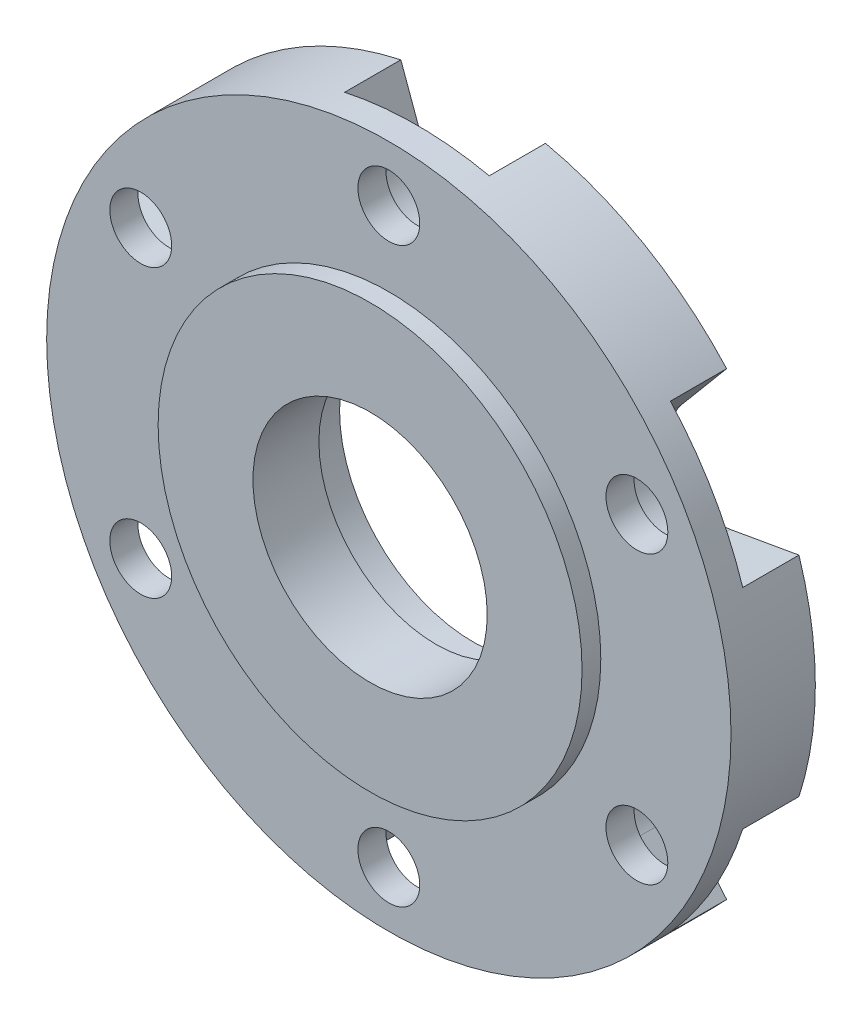
SolidWorks part; units mm, degrees
material "6061-T6 (SS)"
ref_plane "Front Plane" through (0, 0, 0) normal (0, 0, 1) x (1, 0, 0)
ref_plane "Top Plane" through (0, 0, 0) normal (0, 1, 0) x (1, 0, 0)
ref_plane "Right Plane" through (0, 0, 0) normal (1, 0, 0) x (0, 0, -1)
sketch "Sketch Spindle Skeleton" plane through (0, 0, 0) normal (1, 0, 0) x (0, 0, -1)
  line L0 (-95.847, -9.525) -> (-140.95, -9.525)
  line L5 (-1000, 0) -> (49000, 0)
  line L6 (0, -9.525) -> (0, 9.525)
  line L13 (0, 9.525) -> (-45.847, 9.525)
  line L26 (-45.847, 9.525) -> (-45.847, 14)
  line L27 (-45.847, 14) -> (-95.847, 14)
  line L32 (-95.847, 14) -> (-95.847, 9.525)
  line L34 (-160, 7) -> (-160, -7)
  line L36 (-95.847, -9.525) -> (-95.847, -14)
  line L37 (-95.847, -14) -> (-45.847, -14)
  line L38 (-45.847, -14) -> (-45.847, -9.525)
  line L39 (0, -9.525) -> (-45.847, -9.525)
  line L40 (-25.305, 36.5125) -> (-16.305, 36.5125)
  line L41 (-111.341, 22.6187) -> (-95.847, 22.6187)
  line L42 (-111.341, 22.6187) -> (-111.341, -22.6187)
  line L43 (-111.341, -22.6187) -> (-95.847, -22.6187)
  line L44 (-95.847, 22.6187) -> (-95.847, -22.6187)
  line L45 (-111.341, 22.6187) -> (-95.847, -22.6187) construction
  line L46 (-111.341, -22.6187) -> (-95.847, 22.6187) construction
  line L47 (-30.353, 22.6187) -> (-45.847, 22.6187)
  line L48 (-30.353, 22.6187) -> (-30.353, -22.6187)
  line L49 (-30.353, -22.6187) -> (-45.847, -22.6187)
  line L50 (-45.847, 22.6187) -> (-45.847, -22.6187)
  line L51 (-30.353, 22.6187) -> (-45.847, -22.6187) construction
  line L52 (-30.353, -22.6187) -> (-45.847, 22.6187) construction
  line L59 (-16.305, 36.5125) -> (-16.305, -36.5125)
  line L60 (-16.305, -36.5125) -> (-25.305, -36.5125)
  line L61 (-25.305, -22.6187) -> (-27.305, -22.6187)
  line L62 (-27.305, -22.6187) -> (-27.305, -12.5)
  line L63 (-27.305, -12.5) -> (-25.305, -12.5)
  line L64 (-25.305, -12.5) -> (-25.305, 12.5)
  line L65 (-25.305, 12.5) -> (-27.305, 12.5)
  line L66 (-27.305, 12.5) -> (-27.305, 22.6187)
  line L67 (-27.305, 22.6187) -> (-25.305, 22.6187)
  line L68 (-25.305, 22.6187) -> (-25.305, 36.5125)
  line L69 (-25.305, -22.6187) -> (-25.305, -36.5125)
  line L71 (-119.469, 36.5125) -> (-26.305, 36.5125)
  line L72 (-119.469, 36.5125) -> (-119.469, -36.5125)
  line L73 (-119.469, -36.5125) -> (-26.305, -36.5125)
  line L74 (-26.305, 36.5125) -> (-26.305, -36.5125)
  line L75 (-119.469, 36.5125) -> (-26.305, -36.5125) construction
  line L76 (-119.469, -36.5125) -> (-26.305, 36.5125) construction
  line L77 (-140.95, -9.525) -> (-140.95, -7)
  line L78 (-140.95, -7) -> (-160, -7)
  line L79 (-95.847, 9.525) -> (-140.95, 9.525)
  line L80 (-140.95, 7) -> (-160, 7)
  line L81 (-140.95, 9.525) -> (-140.95, 7)
  line L82 (-118.3985, 9.525) -> (-118.3985, -9.525) construction
  line L83 (-22.9235, 9.525) -> (-22.9235, -9.525) construction
  line L96 (-119.469, 36.5125) -> (-134.709, 36.5125)
  line L98 (-119.469, -36.5125) -> (-134.709, -36.5125)
  line L99 (-134.709, 36.5125) -> (-134.709, -36.5125)
  line L110 (-119.469, 36.5125) -> (-119.469, -36.5125)
  point P3 (0, 0)
  point P18 (-103.594, 0)
  point P24 (-38.1, 0)
  point P29 (-72.887, 0)
  point P48 (-16.305, 30.5656)
  point P70 (-134.709, 31.75)
revolve "Main Revolve" add sketch "Sketch Spindle Skeleton" angle 360 about L5 region at (0, 22.8004, 21.005) region at (0, 17.5594, 26.805)
sketch "Sketch Center Cut" plane through (0, 0, 25.305) normal (0, 0, 1) x (1, 0, 0)
  circle A3 centre (0, 0) radius 12.5
  dimension "D1" = 25
extrude "Cut Center" cut sketch "Sketch Center Cut" against normal through all both and the other way through all
hole_wizard "CBORE for M6 SHCS1" positions "Hole wizard sketch 1" profile "Hole wizard sketch 2" counterbore size "M6" standard "ANSI Metric" end condition through all
sketch "Hole wizard sketch 1" plane through (0, 0, 16.305) normal (0, 0, -1) x (-1, 0, 0)
  point P0 (0, 30.5656)
sketch "Hole wizard sketch 2" plane through (0, 30.5656, 16.305) normal (1, 0, 0) x (0, 1, 0)
  line L0 (0, 0) -> (0, 11)
  line L1 (0, 11) -> (3.3, 11)
  line L3 (3.3, 11) -> (3.3, 6)
  line L4 (3.3, 6) -> (5.5, 6)
  line L5 (5.5, 6) -> (5.5, 0)
  line L7 (5.5, 0) -> (0, 0)
  line L11 (0, -6.35) -> (0, 107.95) construction
  dimension "Thru Hole Dia." = 6.6
  dimension "Thru Hole Depth" = 11
  dimension "C'Bore Dia." = 11
  dimension "C'Bore Depth" = 6
pattern_circular "CirPattern1" count 6 over 360 about axis through (0, 0, 16.305) along (0, 0, 1) of "CBORE for M6 SHCS1"
sketch "Sketch1" plane through (0, 0, 16.305) normal (0, 0, -1) x (-1, 0, 0)
  circle A0 centre (0, 0) radius 14.2558
  dimension "D1" = 28.5115
extrude "Cut-Extrude1" cut sketch "Sketch1" against normal blind 3.9624
sketch "Sketch2" plane through (0, 0, 16.305) normal (0, 0, -1) x (-1, 0, 0)
  line L0 (-5.1683, 28.6845) -> (-7.7172, 35.6876)
  line L1 (0, 30.5656) -> (0, 37.65) construction
  line L2 (5.1683, 28.6845) -> (7.7172, 35.6876)
  circle A0 centre (0, 30.5656) radius 5.5 construction
  circle A1 centre (0, 0) radius 36.5125 construction
  arc A2 (-5.1683, 28.6845) -> (5.1683, 28.6845) centre (0, 30.5656) ccw
  point P37 (0.065, 0.0375)
  circle M8 centre (0, 30.5656) radius 5.5
  circle M9 centre (0, 0) radius 36.5125
  dimension "D1" = 20
extrude "Cut-Extrude2" cut sketch "Sketch2" against normal up to surface (6 mm away) contours L1 L2 M8 M9 | L1 L0 M8 M9 region at (4.9613, 34.4886, 16.305) region at (-4.9613, 34.4886, 16.305) up to face at (23.1706, -15.2828, 22.305)
pattern_circular "CirPattern2" count 6 over 360 about axis through (0, 0, 1000) along (0, 0, 1) of "Cut-Extrude2" reverse direction yes
